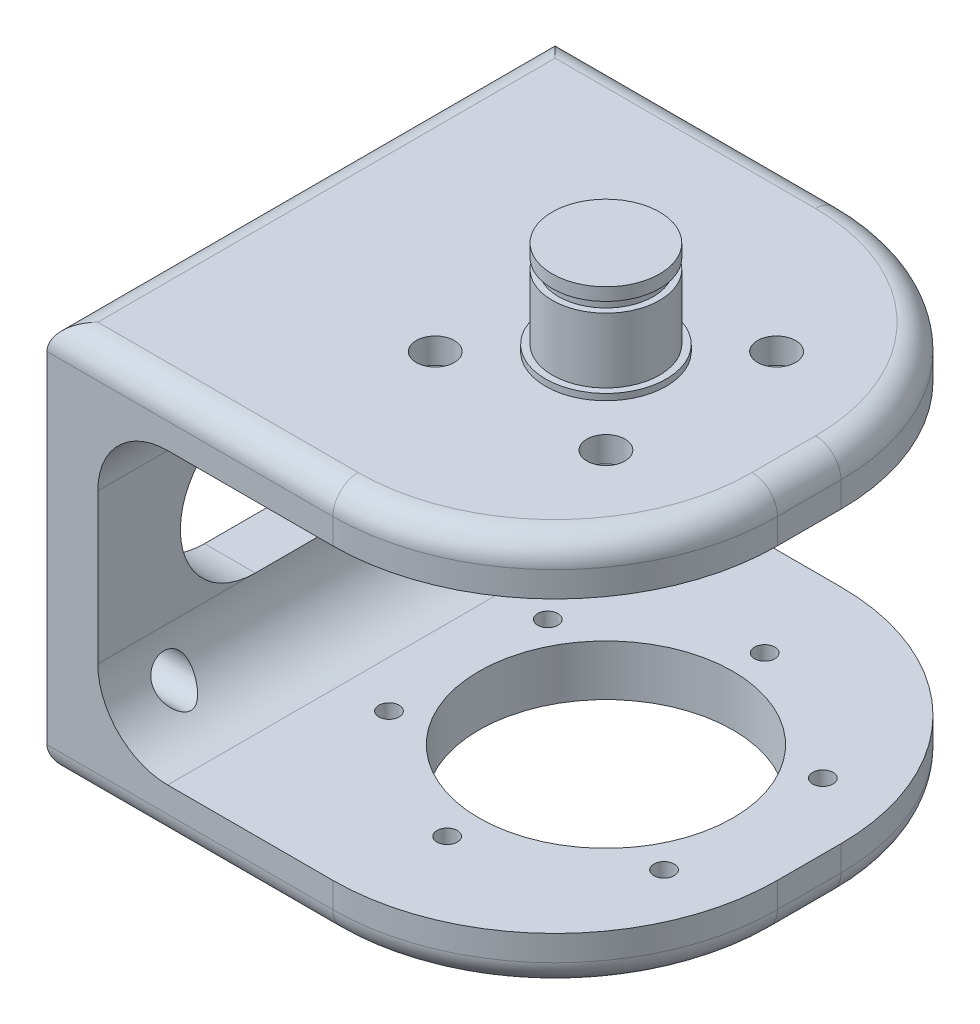
SolidWorks part; units mm, degrees
material "PETG-CF"
ref_plane "Front Plane" through (0, 0, 0) normal (0, 0, 1) x (1, 0, 0)
ref_plane "Top Plane" through (0, 0, 0) normal (0, 1, 0) x (1, 0, 0)
ref_plane "Right Plane" through (0, 0, 0) normal (1, 0, 0) x (0, 0, -1)
sketch "草图1" plane through (0, 0, 0) normal (0, 1, 0) x (1, 0, 0)
  line L1 (40, -40) -> (-40, -40)
  line L2 (40, -40) -> (40, 40)
  line L3 (40, 40) -> (-40, 40)
  line L4 (-40, -40) -> (-40, 40)
  line L5 (40, -40) -> (-40, 40) construction
  line L6 (40, 40) -> (-40, -40) construction
  point P0 (0, 0)
  dimension "D1" = 80
  dimension "D2" = 80
extrude "凸台-拉伸1" add sketch "草图1" along normal blind 8
sketch "草图2" plane through (0, 8, 0) normal (0, 1, 0) x (1, 0, 0)
  line L0 (-40, -40) -> (40, -40) construction
  line L1 (-32, -40) -> (-40, -40)
  line L2 (-32, -40) -> (-32, 40)
  line L3 (-32, 40) -> (-40, 40)
  line L4 (-40, -40) -> (-40, 40)
  line L5 (-32, -40) -> (-40, 40) construction
  line L6 (-32, 40) -> (-40, -40) construction
  point P0 (-36, 0)
  dimension "D1" = 8
extrude "凸台-拉伸2" add sketch "草图2" along normal blind 53.6
sketch "草图5" plane through (-32, 0, 0) normal (1, 0, 0) x (0, 0, -1)
  line L0 (-40, 61.6) -> (-40, 8) construction
  line L1 (40, 53.6) -> (-40, 53.6)
  line L2 (40, 53.6) -> (40, 61.6)
  line L3 (40, 61.6) -> (-40, 61.6)
  line L4 (-40, 53.6) -> (-40, 61.6)
  line L5 (40, 53.6) -> (-40, 61.6) construction
  line L6 (40, 61.6) -> (-40, 53.6) construction
  line L7 (40, 61.6) -> (40, 8) construction
  line L9 (-40, 61.6) -> (40, 61.6) construction
  point P0 (0, 57.6)
  dimension "D1" = 8
extrude "凸台-拉伸3" add sketch "草图5" along normal through all
sketch "草图4" plane through (0, 8, 0) normal (0, 1, 0) x (1, 0, 0)
  line L0 (-40, 40) -> (-40, -40) construction
  line L2 (40, -40) -> (40, 40) construction
  circle A0 centre (8, 0) radius 25 construction
  circle A1 centre (8, 25) radius 1.6
  circle A2 centre (-13.6506, 12.5) radius 1.6
  circle A3 centre (-13.6506, -12.5) radius 1.6
  circle A4 centre (8, -25) radius 1.6
  circle A5 centre (8, 0) radius 20
  circle A6 centre (29.6506, -12.5) radius 1.6
  circle A7 centre (29.6506, 12.5) radius 1.6
  point P17 (8, 0)
  point P22 (-40, 0)
  dimension "D3" = 50
  dimension "D4" = 3.2
  dimension "D6" = 40
  dimension "D1" = 32
  dimension "D5" = 6
extrude "切除-拉伸1" cut sketch "草图4" against normal through all contours A5 | A2 | A1 | A4 | A3 | A7 | A6
sketch "草图7" plane through (0, 61.6, 0) normal (0, 1, 0) x (1, 0, 0)
  line L0 (40, 40) -> (40, -40) construction
  line L3 (8, 0) -> (-5.435, 13.435) construction
  line L4 (8, 0) -> (8, 19) construction
  circle A0 centre (8, 0) radius 19 construction
  circle A5 centre (-5.435, 13.435) radius 1.6
  circle A6 centre (21.435, 13.435) radius 1.6
  circle A7 centre (21.435, -13.435) radius 1.6
  circle A8 centre (-5.435, -13.435) radius 1.6
  point P10 (40, 0)
  point P20 (8, 0)
  dimension "D1" = 38
  dimension "D4" = 45
  dimension "D5" = 3.2
  dimension "D6" = 4
extrude "切除-拉伸3" cut sketch "草图7" against normal up to next
fillet "圆角3" radius 35 4 edges at (40, 4, 40) (40, 4, -40) (40, 57.6, -40) (40, 57.6, 40)
fillet "圆角4" radius 11 2 edges at (-32, 8, 0) (-32, 53.6, 0)
sketch "草图6" plane through (-40, 0, 0) normal (-1, 0, 0) x (0, 0, 1)
  line L1 (30, 13) -> (-30, 13) construction
  line L2 (30, 13) -> (30, 48.6) construction
  line L3 (30, 48.6) -> (-30, 48.6) construction
  line L4 (-30, 13) -> (-30, 48.6) construction
  line L5 (30, 13) -> (-30, 48.6) construction
  line L6 (30, 48.6) -> (-30, 13) construction
  line L8 (40, 61.6) -> (40, 0) construction
  line L9 (-40, 61.6) -> (-40, 0) construction
  line L10 (-30, 30.8) -> (30, 30.8) construction
  line L11 (0, 13) -> (0, 48.6) construction
  line L12 (-40, 61.6) -> (40, 61.6) construction
  line L13 (-40, 0) -> (40, 0) construction
  circle A0 centre (-30, 48.6) radius 1.6
  circle A1 centre (30, 48.6) radius 1.6
  circle A2 centre (30, 13) radius 1.6
  circle A3 centre (-30, 13) radius 1.6
  point P0 (0, 30.8)
  dimension "D5" = 3.2
  dimension "D1" = 13
  dimension "D2" = 13
  dimension "D3" = 10
  dimension "D4" = 10
extrude "切除-拉伸2" cut sketch "草图6" against normal through all
sketch "草图8" plane through (0, 61.6, 0) normal (0, 1, 0) x (1, 0, 0)
  circle A0 centre (8, 0) radius 8.45
  dimension "D1" = 16.9
extrude "凸台-拉伸4" add sketch "草图8" along normal blind 14.8
ref_plane "基准面1" through (0, 74.4, 0) normal (0, 1, 0) x (1, 0, 0)
sketch "草图10" plane through (0, 74.4, 0) normal (0, 1, 0) x (1, 0, 0)
  circle A0 centre (8, 0) radius 8.45
  circle A1 centre (8, 0) radius 7.45
  dimension "D1" = 14.9
extrude "切除-拉伸4" cut sketch "草图10" against normal blind 1.6
ref_plane "基准面2" through (-36, 0, 0) normal (-1, 0, 0) x (0, 0, 1)
sketch "草图12" plane through (-36, 0, 0) normal (-1, 0, 0) x (0, 0, 1)
  line L0 (-40, 30.8) -> (40, 30.8) construction
  line L1 (-40, 61.6) -> (-40, 0) construction
  line L2 (40, 61.6) -> (40, 0) construction
  line L3 (0, 61.6) -> (0, 0) construction
  line L4 (8.45, 61.6) -> (-8.45, 61.6) construction
  circle A0 centre (-30, 48.6) radius 3
  circle A1 centre (30, 48.6) radius 3
  circle A2 centre (30, 13) radius 3
  circle A3 centre (-30, 13) radius 3
  point P13 (0, 0)
  dimension "D1" = 6
extrude "切除-拉伸5" cut sketch "草图12" against normal up to next
sketch "草图14" plane through (0, 61.6, 0) normal (0, 1, 0) x (1, 0, 0)
  circle A0 centre (-5.435, 13.435) radius 3
  circle A1 centre (21.435, 13.435) radius 3
  circle A2 centre (21.435, -13.435) radius 3
  circle A3 centre (-5.435, -13.435) radius 3
  point P12 (8, 0)
  dimension "D1" = 6
  dimension "D2" = 4
sketch "Sketch1" plane through (-32, 0, 0) normal (1, 0, 0) x (0, 0, -1)
  line L0 (15.2, 30.8) -> (-15.2, 30.8) construction
  line L1 (15.2, 19) -> (-15.2, 19)
  line L2 (15.2, 42.6) -> (-15.2, 42.6)
  line L3 (40, 42.6) -> (40, 19) construction
  line L4 (5, 61.6) -> (-5, 61.6) construction
  line L5 (40, 42.6) -> (-40, 42.6) construction
  arc A0 (15.2, 19) -> (15.2, 42.6) centre (15.2, 30.8) ccw
  arc A1 (-15.2, 42.6) -> (-15.2, 19) centre (-15.2, 30.8) ccw
  point P2 (0, 30.8)
  point P12 (40, 30.8)
  point P15 (0, 61.6)
  point P18 (27, 30.8)
  dimension "D1" = 13
extrude "Cut-Extrude1" cut sketch "Sketch1" against normal through all
extrude "切除-拉伸6" cut sketch "草图14" against normal blind 4
sketch "草图15" plane through (0, 0, 0) normal (0, -1, 0) x (1, 0, 0)
  circle A0 centre (-13.6506, 12.5) radius 3
  circle A1 centre (8, 25) radius 3
  circle A2 centre (29.6506, 12.5) radius 3
  circle A3 centre (29.6506, -12.5) radius 3
  circle A4 centre (8, -25) radius 3
  circle A5 centre (-13.6506, -12.5) radius 3
  point P15 (8, 0)
  dimension "D1" = 6
  dimension "D2" = 6
extrude "切除-拉伸7" cut sketch "草图15" against normal blind 4
sketch "草图16" plane through (0, 61.6, 0) normal (0, 1, 0) x (1, 0, 0)
  circle A0 centre (8, 0) radius 9.5
  dimension "D1" = 19
extrude "凸台-拉伸5" add sketch "草图16" along normal blind 1
fillet "Fillet2" radius 4 12 edges at (-17.5, 0, -40) (29.7487, 0, -29.7487) (40, 0, 0) (29.7487, 0, 29.7487) (-17.5, 61.6, 40) (-17.5, 61.6, -40) (29.7487, 61.6, -29.7487) (40, 61.6, 0) (-40, 61.6, 0) (-40, 0, 0) (-17.5, 0, 40) (29.7487, 61.6, 29.7487)
